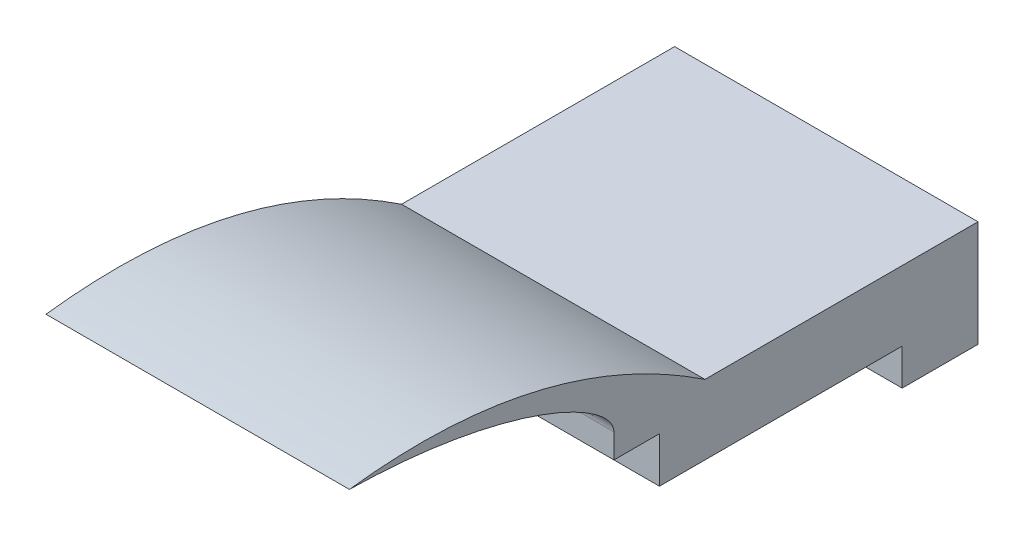
SolidWorks part; units mm, degrees
material "ABS"
ref_plane "Front Plane" through (0, 0, 0) normal (0, 0, 1) x (1, 0, 0)
ref_plane "Top Plane" through (0, 0, 0) normal (0, 1, 0) x (1, 0, 0)
ref_plane "Right Plane" through (0, 0, 0) normal (1, 0, 0) x (0, 0, -1)
curve "Curve1"
  spline degree 3 poles (0, 0.0012, 1.0003) (0, 0.0015, 0.9994) (0, 0.0028, 0.9958) (0, 0.0055, 0.9879) (0, 0.0099, 0.9747) (0, 0.0159, 0.9565) (0, 0.0233, 0.9333) (0, 0.0318, 0.9054) (0, 0.0411, 0.8731) (0, 0.051, 0.8366) (0, 0.0612, 0.7964) (0, 0.0713, 0.7528) (0, 0.0811, 0.7063) (0, 0.0903, 0.6574) (0, 0.0985, 0.6067) (0, 0.1057, 0.5546) (0, 0.1115, 0.5018) (0, 0.1158, 0.4488) (0, 0.1186, 0.3959) (0, 0.1189, 0.3436) (0, 0.1164, 0.2927) (0, 0.1112, 0.2442) (0, 0.1037, 0.1988) (0, 0.0942, 0.157) (0, 0.0831, 0.1194) (0, 0.0711, 0.0865) (0, 0.0584, 0.0585) (0, 0.0457, 0.0357) (0, 0.0334, 0.0184) (0, 0.0218, 0.0064) (0, 0.0108, -0.0005) (0, -0.0003, -0.0011) (0, -0.0092, 0.0055) (0, -0.0148, 0.017) (0, -0.0185, 0.0329) (0, -0.0204, 0.0533) (0, -0.0208, 0.0781) (0, -0.0198, 0.107) (0, -0.0176, 0.1398) (0, -0.0147, 0.176) (0, -0.0111, 0.2153) (0, -0.0074, 0.2574) (0, -0.0037, 0.3019) (0, -0.0005, 0.3484) (0, 0.002, 0.397) (0, 0.0037, 0.4471) (0, 0.0055, 0.4983) (0, 0.0069, 0.5496) (0, 0.0079, 0.6006) (0, 0.0085, 0.6505) (0, 0.0086, 0.699) (0, 0.0083, 0.7455) (0, 0.0076, 0.7894) (0, 0.0065, 0.8302) (0, 0.0053, 0.8675) (0, 0.0039, 0.9007) (0, 0.0027, 0.9296) (0, 0.0013, 0.9539) (0, 0.0006, 0.9727) (0, -0.0011, 0.9872) (0, 0, 0.9944) (0, -0.002, 0.9999) (0, -0.0005, 1) (0, 0, 1) knots 0 0 0 0 0.001372 0.005465 0.012235 0.021602 0.033461 0.047671 0.064081 0.082496 0.102719 0.124527 0.147676 0.171913 0.196978 0.222597 0.248497 0.274385 0.300041 0.32569 0.350525 0.37428 0.396711 0.417577 0.436654 0.453744 0.46868 0.481329 0.491631 0.499616 0.505546 0.510185 0.514824 0.520702 0.528516 0.538466 0.550543 0.564643 0.580638 0.598345 0.617584 0.638174 0.659922 0.682632 0.706121 0.730727 0.7557 0.780732 0.805564 0.829932 0.85357 0.876213 0.89761 0.917519 0.935698 0.951943 0.966047 0.97784 0.987174 0.993932 0.998018 0.999386 1 1 1 1
sketch "Sketch1" plane through (0, 0, 0) normal (1, 0, 0) x (0, 0, -1)
  line L1 (9.9533, 1.5275) -> (9.9533, -8.6325)
  line L3 (48.0533, 1.5275) -> (48.0533, -42.9225)
  line L4 (48.0533, -42.9225) -> (29.0033, -42.9225)
  line L5 (29.0033, -42.9225) -> (29.0033, -8.6325)
  line L6 (29.0033, -8.6325) -> (9.9533, -8.6325)
  line L8 (69.85, 0) -> (-69.85, 0) construction
  line L10 (0, 46.7282) -> (0, -46.7282) construction
  spline S0 degree 2 poles (-100.7907, 36.068) (-19.0327, 46.3014) (48.0533, 1.5275) knots 0 0 0 1 1 1
  spline S1 degree 3 poles (-100.7907, 36.068) (-95.472, 35.9701) (-84.3352, 35.4975) (-67.8427, 33.9153) (-51.8361, 31.4045) (-37.3694, 28.2078) (-24.621, 24.5005) (-13.7375, 20.4579) (-4.8312, 16.2565) (2.0481, 12.0631) (6.8584, 7.9761) (9.4175, 4.4356) (9.9102, 2.2026) (9.9533, 1.5275) knots 0.353791 0.353791 0.353791 0.353791 0.37428 0.396711 0.417577 0.436654 0.453744 0.46868 0.481329 0.491631 0.499616 0.505546 0.508115 0.508115 0.508115 0.508115
  dimension "D2" = 1.5275
  dimension "D3" = 10.16
  dimension "D5" = 100.7907
  dimension "D6" = 38.1
  dimension "D7" = 44.45
  dimension "D8" = 34.29
  dimension "D9" = 19.05
  dimension "D10" = 29.1024
  dimension "D11" = 9.7768
  dimension "D12" = 48.0533
  dimension "D14" = 36.068
extrude "Boss-Extrude1" add sketch "Sketch1" along normal mid plane 127
sketch "Sketch2" plane through (0, 0, -48.0533) normal (0, 0, -1) x (-1, 0, 0)
  line L0 (-63.5, -19.3005) -> (-31.75, -19.3005) construction
  line L1 (-63.5, -42.9225) -> (-63.5, 1.5275) construction
  line L2 (-31.75, -19.3005) -> (31.75, -19.3005) construction
  line L3 (31.75, -19.3005) -> (63.5, -19.3005) construction
  line L4 (63.5, -42.9225) -> (63.5, 1.5275) construction
  line L5 (-63.5, 1.5275) -> (63.5, 1.5275) construction
  circle A0 centre (-31.75, -19.3005) radius 3.175
  circle A1 centre (31.75, -19.3005) radius 3.175
  dimension "D1" = 6.35
  dimension "D2" = 63.5
  dimension "D3" = 20.828
extrude "Cut-Extrude1" cut sketch "Sketch2" against normal through all both and the other way through all
sketch "Sketch3" plane through (0, 0, -48.0533) normal (0, 0, -1) x (-1, 0, 0)
  line L4 (63.5, -42.9225) -> (63.5, 1.5275)
  line L5 (63.5, 1.5275) -> (-63.5, 1.5275)
  line L6 (-63.5, 1.5275) -> (-63.5, -42.9225)
  line L7 (-63.5, -42.9225) -> (63.5, -42.9225)
  line L8 (63.5, -42.9225) -> (63.5, 1.5275)
  line L9 (63.5, 1.5275) -> (-63.5, 1.5275)
  line L10 (-63.5, 1.5275) -> (-63.5, -42.9225)
  line L11 (-63.5, -42.9225) -> (63.5, -42.9225)
  circle A0 centre (-31.75, -19.3005) radius 3.175 construction
  circle A1 centre (-31.75, -19.3005) radius 3.175
  circle A2 centre (31.75, -19.3005) radius 3.175 construction
  circle A3 centre (31.75, -19.3005) radius 3.175
  dimension "D1" = 0
extrude "Boss-Extrude2" add sketch "Sketch3" along normal blind 114.3
sketch "Sketch4" plane through (-63.5, 0, 0) normal (-1, 0, 0) x (0, 0, 1)
  line L1 (-29.0033, -42.9225) -> (-130.6033, -42.9225)
  line L2 (-29.0033, -42.9225) -> (-29.0033, -27.6825)
  line L3 (-29.0033, -27.6825) -> (-130.6033, -27.6825)
  line L4 (-130.6033, -42.9225) -> (-130.6033, -27.6825)
  dimension "D1" = 101.6
  dimension "D2" = 15.24
extrude "Cut-Extrude2" cut sketch "Sketch4" against normal through all
